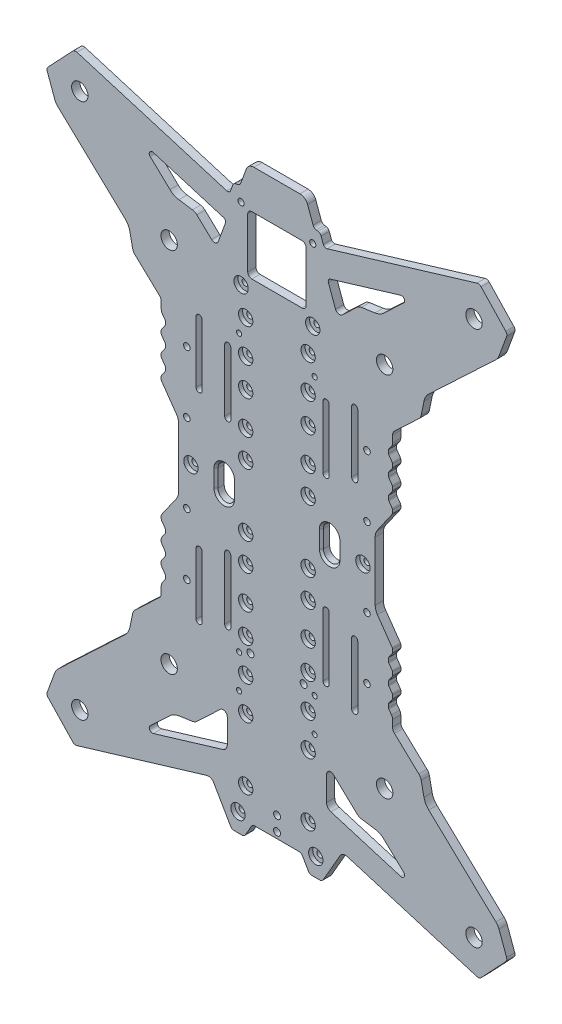
SolidWorks part; units mm, degrees
ref_plane "Front Plane" through (0, 0, 0) normal (0, 0, 1) x (1, 0, 0)
ref_plane "Top Plane" through (0, 0, 0) normal (0, 1, 0) x (1, 0, 0)
ref_plane "Right Plane" through (0, 0, 0) normal (1, 0, 0) x (0, 0, -1)
sketch "Model" plane through (0, 0, 0) normal (0, 0, 1) x (1, 0, 0)
  line L0 (183.8108, 197.417) -> (183.8108, 227.917)
  line L1 (186.8108, 227.917) -> (186.8108, 197.417)
  line L2 (138.8108, 139.917) -> (138.8108, 109.417)
  line L3 (135.8108, 109.417) -> (135.8108, 139.917)
  line L4 (186.8108, 139.917) -> (186.8108, 109.417)
  line L5 (183.8108, 109.417) -> (183.8108, 139.917)
  line L6 (135.8108, 197.417) -> (135.8108, 227.917)
  line L7 (138.8108, 227.917) -> (138.8108, 197.417)
  line L8 (147.0608, 264.0945) -> (147.0608, 288.5945)
  line L9 (173.5608, 262.0945) -> (149.0608, 262.0945)
  line L10 (175.5608, 288.5945) -> (175.5608, 264.0945)
  line L11 (149.0608, 290.5945) -> (173.5608, 290.5945)
  line L12 (133.6884, 72.3677) -> (122.1935, 61.5247)
  line L13 (120.0282, 60.4766) -> (113.4215, 59.5095)
  line L14 (100.8847, 45.7661) -> (134.926, 56.02)
  line L15 (209.2, 59.5095) -> (202.5933, 60.4766)
  line L16 (200.428, 61.5247) -> (188.9331, 72.3677)
  line L17 (185.5608, 58.8925) -> (185.5608, 70.9128)
  line L18 (187.6955, 56.02) -> (221.7368, 45.7661)
  line L19 (223.1987, 48.2935) -> (213.5306, 57.4133)
  line L20 (113.4215, 277.8244) -> (120.0282, 276.8573)
  line L21 (122.1935, 275.8092) -> (129.4288, 268.9842)
  line L22 (135.174, 281.2392) -> (100.8847, 291.5678)
  line L23 (99.4228, 289.0404) -> (109.0909, 279.9206)
  line L24 (261.0344, 314.783) -> (273.0616, 302.0327)
  line L25 (273.4849, 299.9728) -> (269.7846, 289.8648)
  line L26 (268.2674, 287.5628) -> (235.4884, 256.6428)
  line L27 (233.1432, 252.4417) -> (231.7925, 245.9027)
  line L28 (230.6199, 243.8022) -> (218.7522, 232.6075)
  line L29 (217.8108, 230.4252) -> (217.8108, 227.2161)
  line L30 (217.2682, 225.4954) -> (215.9916, 223.6722)
  line L31 (215.8108, 223.0986) -> (215.8108, 221.7292)
  line L32 (215.9916, 221.1557) -> (217.6299, 218.8159)
  line L33 (217.8108, 218.2423) -> (217.8108, 216.8729)
  line L34 (217.6299, 216.2994) -> (215.9916, 213.9596)
  line L35 (215.8108, 213.386) -> (215.8108, 212.0166)
  line L36 (215.9916, 211.4431) -> (217.6299, 209.1033)
  line L37 (217.8108, 208.5298) -> (217.8108, 207.1603)
  line L38 (217.6299, 206.5868) -> (215.9916, 204.247)
  line L39 (215.8108, 203.6735) -> (215.8108, 202.304)
  line L40 (215.9916, 201.7305) -> (217.6299, 199.3907)
  line L41 (217.8108, 198.8172) -> (217.8108, 197.4478)
  line L42 (217.6299, 196.8742) -> (210.3959, 186.5429)
  line L43 (209.3108, 183.1014) -> (209.3108, 154.2325)
  line L44 (210.3959, 150.791) -> (217.6299, 140.4597)
  line L45 (217.8108, 139.8861) -> (217.8108, 138.5167)
  line L46 (217.6299, 137.9432) -> (215.9916, 135.6034)
  line L47 (215.8108, 135.0299) -> (215.8108, 133.6605)
  line L48 (215.9916, 133.0869) -> (217.6299, 130.7471)
  line L49 (217.8108, 130.1736) -> (217.8108, 128.8042)
  line L50 (217.6299, 128.2306) -> (215.9916, 125.8908)
  line L51 (215.8108, 125.3173) -> (215.8108, 123.9479)
  line L52 (215.9916, 123.3743) -> (217.6299, 121.0345)
  line L53 (217.8108, 120.461) -> (217.8108, 119.0916)
  line L54 (217.6299, 118.518) -> (215.9916, 116.1782)
  line L55 (215.8108, 115.6047) -> (215.8108, 114.2353)
  line L56 (215.9916, 113.6617) -> (217.2682, 111.8385)
  line L57 (217.8108, 110.1178) -> (217.8108, 106.9087)
  line L58 (218.7522, 104.7264) -> (230.6199, 93.5317)
  line L59 (231.7925, 91.4312) -> (233.1432, 84.8922)
  line L60 (235.4884, 80.6911) -> (268.2674, 49.7711)
  line L61 (269.7846, 47.4691) -> (273.4849, 37.3611)
  line L62 (273.0616, 35.3012) -> (261.0344, 22.5509)
  line L63 (259.0027, 22.0083) -> (195.64, 41.0944)
  line L64 (192.1766, 39.7219) -> (183.942, 25.4591)
  line L65 (182.2099, 24.4591) -> (178.4116, 24.4591)
  line L66 (176.6796, 25.4591) -> (173.7928, 30.4591)
  line L67 (172.0608, 31.4591) -> (150.5608, 31.4591)
  line L68 (148.8287, 30.4591) -> (145.942, 25.4591)
  line L69 (144.2099, 24.4591) -> (140.4116, 24.4591)
  line L70 (138.6796, 25.4591) -> (130.4449, 39.7219)
  line L71 (126.9816, 41.0944) -> (63.6188, 22.0083)
  line L72 (61.5871, 22.5509) -> (49.5599, 35.3012)
  line L73 (49.1366, 37.3611) -> (52.8369, 47.4691)
  line L74 (54.3542, 49.7711) -> (87.1331, 80.6911)
  line L75 (89.4783, 84.8922) -> (90.8291, 91.4312)
  line L76 (92.0016, 93.5317) -> (103.8693, 104.7264)
  line L77 (104.8108, 106.9087) -> (104.8108, 110.1178)
  line L78 (105.3533, 111.8385) -> (106.6299, 113.6617)
  line L79 (106.8108, 114.2353) -> (106.8108, 115.6047)
  line L80 (106.6299, 116.1782) -> (104.9916, 118.518)
  line L81 (104.8108, 119.0916) -> (104.8108, 120.461)
  line L82 (104.9916, 121.0345) -> (106.6299, 123.3743)
  line L83 (106.6299, 125.8908) -> (104.9916, 128.2306)
  line L84 (104.8108, 128.8042) -> (104.8108, 130.1736)
  line L85 (104.9916, 130.7471) -> (106.6299, 133.0869)
  line L86 (106.8108, 133.6605) -> (106.8108, 135.0299)
  line L87 (106.6299, 135.6034) -> (104.9916, 137.9432)
  line L88 (104.8108, 138.5167) -> (104.8108, 139.8861)
  line L89 (104.9916, 140.4597) -> (112.2257, 150.791)
  line L90 (113.3108, 154.2325) -> (113.3108, 183.1014)
  line L91 (112.2257, 186.5429) -> (104.9916, 196.8742)
  line L92 (104.8108, 197.4478) -> (104.8108, 198.8172)
  line L93 (104.9916, 199.3907) -> (106.6299, 201.7305)
  line L94 (106.8108, 202.304) -> (106.8108, 203.6735)
  line L95 (106.6299, 204.247) -> (104.9916, 206.5868)
  line L96 (104.8108, 207.1603) -> (104.8108, 208.5298)
  line L97 (104.9916, 209.1033) -> (106.6299, 211.4431)
  line L98 (106.8108, 212.0166) -> (106.8108, 213.386)
  line L99 (106.6299, 213.9596) -> (104.9916, 216.2994)
  line L100 (104.8108, 216.8729) -> (104.8108, 218.2423)
  line L101 (104.9916, 218.8159) -> (106.6299, 221.1557)
  line L102 (106.8108, 221.7292) -> (106.8108, 223.0986)
  line L103 (106.6299, 223.6722) -> (105.3533, 225.4954)
  line L104 (104.8108, 227.2161) -> (104.8108, 230.4252)
  line L105 (103.8693, 232.6075) -> (92.0016, 243.8022)
  line L106 (90.8291, 245.9027) -> (89.4783, 252.4417)
  line L107 (87.1331, 256.6428) -> (54.3542, 287.5628)
  line L108 (52.8369, 289.8648) -> (49.1366, 299.9728)
  line L109 (49.5599, 302.0327) -> (61.5871, 314.783)
  line L110 (63.6188, 315.3256) -> (136.8099, 293.279)
  line L111 (138.6521, 294.2022) -> (139.728, 297.1583)
  line L112 (141.2601, 298.4439) -> (142.113, 298.5943)
  line L113 (143.6451, 299.8798) -> (146.325, 307.2429)
  line L114 (150.0838, 309.8748) -> (172.5378, 309.8748)
  line L115 (176.2965, 307.2429) -> (178.9765, 299.8798)
  line L116 (180.5086, 298.5943) -> (181.3614, 298.4439)
  line L117 (185.8116, 293.279) -> (259.0027, 315.3256)
  line L118 (193.1927, 268.9842) -> (200.428, 275.8092)
  line L119 (202.5933, 276.8573) -> (209.2, 277.8244)
  line L120 (221.7368, 291.5678) -> (187.4475, 281.2392)
  line L121 (186.4706, 279.2899) -> (189.941, 269.7551)
  line L122 (106.8108, 123.9479) -> (106.8108, 125.3173)
  line L123 (137.0608, 70.9128) -> (137.0608, 58.8925)
  line L124 (109.0909, 57.4133) -> (99.4228, 48.2935)
  line L125 (132.6805, 269.7551) -> (136.1509, 279.2899)
  line L126 (182.8935, 297.1583) -> (183.9694, 294.2022)
  line L127 (213.5306, 279.9206) -> (223.1987, 289.0404)
  circle A0 centre (178.8108, 292.022) radius 1.5
  arc A1 (183.8108, 197.417) -> (186.8108, 197.417) centre (185.3108, 197.417) ccw
  arc A2 (186.8108, 227.917) -> (183.8108, 227.917) centre (185.3108, 227.917) ccw
  arc A3 (138.8108, 139.917) -> (135.8108, 139.917) centre (137.3108, 139.917) ccw
  arc A4 (135.8108, 109.417) -> (138.8108, 109.417) centre (137.3108, 109.417) ccw
  circle A5 centre (213.9455, 258.3167) radius 4
  circle A6 centre (257.5914, 299.4875) radius 4
  circle A7 centre (65.0301, 299.4875) radius 4
  circle A8 centre (108.6761, 258.3167) radius 4
  circle A9 centre (108.6761, 79.0172) radius 4
  circle A10 centre (65.0301, 37.8464) radius 4
  circle A11 centre (257.5914, 37.8464) radius 4
  circle A12 centre (213.9455, 79.0172) radius 4
  arc A13 (186.8108, 139.917) -> (183.8108, 139.917) centre (185.3108, 139.917) ccw
  arc A14 (183.8108, 109.417) -> (186.8108, 109.417) centre (185.3108, 109.417) ccw
  arc A15 (135.8108, 197.417) -> (138.8108, 197.417) centre (137.3108, 197.417) ccw
  arc A16 (138.8108, 227.917) -> (135.8108, 227.917) centre (137.3108, 227.917) ccw
  circle A17 centre (143.8108, 292.022) radius 1.5
  arc A18 (147.0608, 264.0945) -> (149.0608, 262.0945) centre (149.0608, 264.0945) ccw
  arc A19 (173.5608, 262.0945) -> (175.5608, 264.0945) centre (173.5608, 264.0945) ccw
  arc A20 (175.5608, 288.5945) -> (173.5608, 290.5945) centre (173.5608, 288.5945) ccw
  arc A21 (149.0608, 290.5945) -> (147.0608, 288.5945) centre (149.0608, 288.5945) ccw
  circle A22 centre (146.0608, 227.917) radius 3.5 construction
  circle A23 centre (176.5608, 227.917) radius 3.5 construction
  circle A24 centre (176.5608, 197.417) radius 3.5 construction
  circle A25 centre (146.0608, 197.417) radius 3.5 construction
  circle A26 centre (119.3108, 168.667) radius 3.5 construction
  circle A27 centre (203.3108, 168.667) radius 3.5 construction
  circle A28 centre (146.0608, 183.917) radius 3.5 construction
  circle A29 centre (176.5608, 183.917) radius 3.5 construction
  circle A30 centre (146.0608, 153.417) radius 3.5 construction
  circle A31 centre (176.5608, 153.417) radius 3.5 construction
  circle A32 centre (146.0608, 139.917) radius 3.5 construction
  circle A33 centre (176.5608, 139.917) radius 3.5 construction
  circle A34 centre (146.0608, 109.417) radius 3.5 construction
  circle A35 centre (176.5608, 109.417) radius 3.5 construction
  circle A36 centre (146.0608, 76.667) radius 3.5 construction
  circle A37 centre (176.5608, 76.667) radius 3.5 construction
  circle A38 centre (146.0608, 46.167) radius 3.5 construction
  circle A39 centre (176.5608, 46.167) radius 3.5 construction
  circle A40 centre (142.3108, 33.4591) radius 3.5 construction
  circle A41 centre (180.3108, 33.4591) radius 3.5 construction
  circle A42 centre (176.5608, 93.042) radius 3.5 construction
  circle A43 centre (146.0608, 93.042) radius 3.5 construction
  circle A44 centre (176.5608, 123.542) radius 3.5 construction
  circle A45 centre (146.0608, 123.542) radius 3.5 construction
  circle A46 centre (176.5608, 213.792) radius 3.5 construction
  circle A47 centre (146.0608, 213.792) radius 3.5 construction
  circle A48 centre (176.5608, 244.292) radius 3.5 construction
  circle A49 centre (146.0608, 244.292) radius 3.5 construction
  circle A50 centre (178.8108, 257.022) radius 3.5 construction
  circle A51 centre (143.8108, 257.022) radius 3.5 construction
  arc A52 (137.0608, 70.9128) -> (133.6884, 72.3677) centre (135.0608, 70.9128) ccw
  arc A53 (120.0282, 60.4766) -> (122.1935, 61.5247) centre (119.4488, 64.4344) ccw
  arc A54 (113.4215, 59.5095) -> (109.0909, 57.4133) centre (114.5803, 51.5938) ccw
  arc A55 (99.4228, 48.2935) -> (100.8847, 45.7661) centre (100.4521, 47.2023) ccw
  arc A56 (134.926, 56.02) -> (137.0608, 58.8925) centre (134.0608, 58.8925) ccw
  arc A57 (200.428, 61.5247) -> (202.5933, 60.4766) centre (203.1727, 64.4344) ccw
  arc A58 (188.9331, 72.3677) -> (185.5608, 70.9128) centre (187.5608, 70.9128) ccw
  arc A59 (185.5608, 58.8925) -> (187.6955, 56.02) centre (188.5608, 58.8925) ccw
  arc A60 (221.7368, 45.7661) -> (223.1987, 48.2935) centre (222.1695, 47.2023) ccw
  arc A61 (213.5306, 57.4133) -> (209.2, 59.5095) centre (208.0412, 51.5938) ccw
  arc A62 (122.1935, 275.8092) -> (120.0282, 276.8573) centre (119.4488, 272.8995) ccw
  arc A63 (129.4288, 268.9842) -> (132.6805, 269.7551) centre (130.8012, 270.4391) ccw
  arc A64 (136.1509, 279.2899) -> (135.174, 281.2392) centre (134.7414, 279.8029) ccw
  arc A65 (100.8847, 291.5678) -> (99.4228, 289.0404) centre (100.4521, 290.1316) ccw
  arc A66 (109.0909, 279.9206) -> (113.4215, 277.8244) centre (114.5803, 285.7401) ccw
  arc A67 (261.0344, 314.783) -> (259.0027, 315.3256) centre (259.5795, 313.4106) ccw
  arc A68 (273.4849, 299.9728) -> (273.0616, 302.0327) centre (271.6068, 300.6603) ccw
  arc A69 (268.2674, 287.5628) -> (269.7846, 289.8648) centre (264.1503, 291.9274) ccw
  arc A70 (235.4884, 256.6428) -> (233.1432, 252.4417) centre (240.9778, 250.8233) ccw
  arc A71 (230.6199, 243.8022) -> (231.7925, 245.9027) centre (227.8752, 246.7119) ccw
  arc A72 (218.7522, 232.6075) -> (217.8108, 230.4252) centre (220.8108, 230.4252) ccw
  arc A73 (217.2682, 225.4954) -> (217.8108, 227.2161) centre (214.8108, 227.2161) ccw
  arc A74 (215.9916, 223.6722) -> (215.8108, 223.0986) centre (216.8108, 223.0986) ccw
  arc A75 (215.8108, 221.7292) -> (215.9916, 221.1557) centre (216.8108, 221.7292) ccw
  arc A76 (217.8108, 218.2423) -> (217.6299, 218.8159) centre (216.8108, 218.2423) ccw
  arc A77 (217.6299, 216.2994) -> (217.8108, 216.8729) centre (216.8108, 216.8729) ccw
  arc A78 (215.9916, 213.9596) -> (215.8108, 213.386) centre (216.8108, 213.386) ccw
  arc A79 (215.8108, 212.0166) -> (215.9916, 211.4431) centre (216.8108, 212.0166) ccw
  arc A80 (217.8108, 208.5298) -> (217.6299, 209.1033) centre (216.8108, 208.5298) ccw
  arc A81 (217.6299, 206.5868) -> (217.8108, 207.1603) centre (216.8108, 207.1603) ccw
  arc A82 (215.9916, 204.247) -> (215.8108, 203.6735) centre (216.8108, 203.6735) ccw
  arc A83 (215.8108, 202.304) -> (215.9916, 201.7305) centre (216.8108, 202.3041) ccw
  arc A84 (217.8108, 198.8172) -> (217.6299, 199.3907) centre (216.8108, 198.8172) ccw
  arc A85 (217.6299, 196.8742) -> (217.8108, 197.4478) centre (216.8108, 197.4478) ccw
  arc A86 (210.3959, 186.5429) -> (209.3108, 183.1014) centre (215.3108, 183.1014) ccw
  arc A87 (209.3108, 154.2325) -> (210.3959, 150.791) centre (215.3108, 154.2325) ccw
  arc A88 (217.8108, 139.8861) -> (217.6299, 140.4597) centre (216.8108, 139.8861) ccw
  arc A89 (217.6299, 137.9432) -> (217.8108, 138.5167) centre (216.8108, 138.5167) ccw
  arc A90 (215.9916, 135.6034) -> (215.8108, 135.0299) centre (216.8108, 135.0299) ccw
  arc A91 (215.8108, 133.6605) -> (215.9916, 133.0869) centre (216.8108, 133.6604) ccw
  arc A92 (217.8108, 130.1736) -> (217.6299, 130.7471) centre (216.8108, 130.1736) ccw
  arc A93 (217.6299, 128.2306) -> (217.8108, 128.8042) centre (216.8108, 128.8042) ccw
  arc A94 (215.9916, 125.8908) -> (215.8108, 125.3173) centre (216.8108, 125.3173) ccw
  arc A95 (215.8108, 123.9479) -> (215.9916, 123.3743) centre (216.8108, 123.9479) ccw
  arc A96 (217.8108, 120.461) -> (217.6299, 121.0345) centre (216.8108, 120.461) ccw
  arc A97 (217.6299, 118.518) -> (217.8108, 119.0916) centre (216.8108, 119.0916) ccw
  arc A98 (215.9916, 116.1782) -> (215.8108, 115.6047) centre (216.8108, 115.6047) ccw
  arc A99 (215.8108, 114.2353) -> (215.9916, 113.6617) centre (216.8108, 114.2353) ccw
  arc A100 (217.8108, 110.1178) -> (217.2682, 111.8385) centre (214.8108, 110.1178) ccw
  arc A101 (217.8108, 106.9087) -> (218.7522, 104.7264) centre (220.8108, 106.9087) ccw
  arc A102 (231.7925, 91.4312) -> (230.6199, 93.5317) centre (227.8752, 90.622) ccw
  arc A103 (233.1432, 84.8922) -> (235.4884, 80.6911) centre (240.9778, 86.5106) ccw
  arc A104 (269.7846, 47.4691) -> (268.2674, 49.7711) centre (264.1503, 45.4065) ccw
  arc A105 (273.0616, 35.3012) -> (273.4849, 37.3611) centre (271.6068, 36.6736) ccw
  arc A106 (259.0027, 22.0083) -> (261.0344, 22.5509) centre (259.5795, 23.9233) ccw
  arc A107 (195.64, 41.0944) -> (192.1766, 39.7219) centre (194.7747, 38.2219) ccw
  arc A108 (182.2099, 24.4591) -> (183.942, 25.4591) centre (182.2099, 26.4591) ccw
  arc A109 (176.6796, 25.4591) -> (178.4116, 24.4591) centre (178.4116, 26.4591) ccw
  arc A110 (173.7928, 30.4591) -> (172.0608, 31.4591) centre (172.0608, 29.4591) ccw
  arc A111 (150.5608, 31.4591) -> (148.8287, 30.4591) centre (150.5608, 29.4591) ccw
  arc A112 (144.2099, 24.4591) -> (145.942, 25.4591) centre (144.2099, 26.4591) ccw
  arc A113 (138.6796, 25.4591) -> (140.4116, 24.4591) centre (140.4116, 26.4591) ccw
  arc A114 (130.4449, 39.7219) -> (126.9816, 41.0944) centre (127.8468, 38.2219) ccw
  arc A115 (61.5871, 22.5509) -> (63.6188, 22.0083) centre (63.042, 23.9233) ccw
  arc A116 (49.1366, 37.3611) -> (49.5599, 35.3012) centre (51.0147, 36.6736) ccw
  arc A117 (54.3542, 49.7711) -> (52.8369, 47.4691) centre (58.4712, 45.4065) ccw
  arc A118 (87.1331, 80.6911) -> (89.4783, 84.8922) centre (81.6437, 86.5106) ccw
  arc A119 (92.0016, 93.5317) -> (90.8291, 91.4312) centre (94.7464, 90.622) ccw
  arc A120 (103.8693, 104.7264) -> (104.8108, 106.9087) centre (101.8108, 106.9087) ccw
  arc A121 (105.3533, 111.8385) -> (104.8108, 110.1178) centre (107.8108, 110.1178) ccw
  arc A122 (106.6299, 113.6617) -> (106.8108, 114.2353) centre (105.8108, 114.2353) ccw
  arc A123 (106.8108, 115.6047) -> (106.6299, 116.1782) centre (105.8108, 115.6047) ccw
  arc A124 (104.8108, 119.0916) -> (104.9916, 118.518) centre (105.8108, 119.0916) ccw
  arc A125 (104.9916, 121.0345) -> (104.8108, 120.461) centre (105.8108, 120.461) ccw
  arc A126 (106.6299, 123.3743) -> (106.8108, 123.9479) centre (105.8108, 123.9479) ccw
  arc A127 (106.8108, 125.3173) -> (106.6299, 125.8908) centre (105.8108, 125.3173) ccw
  arc A128 (104.8108, 128.8042) -> (104.9916, 128.2306) centre (105.8108, 128.8042) ccw
  arc A129 (104.9916, 130.7471) -> (104.8108, 130.1736) centre (105.8108, 130.1736) ccw
  arc A130 (106.6299, 133.0869) -> (106.8108, 133.6605) centre (105.8108, 133.6604) ccw
  arc A131 (106.8108, 135.0299) -> (106.6299, 135.6034) centre (105.8108, 135.0299) ccw
  arc A132 (104.8108, 138.5167) -> (104.9916, 137.9432) centre (105.8108, 138.5167) ccw
  arc A133 (104.9916, 140.4597) -> (104.8108, 139.8861) centre (105.8108, 139.8861) ccw
  arc A134 (112.2257, 150.791) -> (113.3108, 154.2325) centre (107.3108, 154.2325) ccw
  arc A135 (113.3108, 183.1014) -> (112.2257, 186.5429) centre (107.3108, 183.1014) ccw
  arc A136 (104.8108, 197.4478) -> (104.9916, 196.8742) centre (105.8108, 197.4478) ccw
  arc A137 (104.9916, 199.3907) -> (104.8108, 198.8172) centre (105.8108, 198.8172) ccw
  arc A138 (106.6299, 201.7305) -> (106.8108, 202.304) centre (105.8108, 202.3041) ccw
  arc A139 (106.8108, 203.6735) -> (106.6299, 204.247) centre (105.8108, 203.6735) ccw
  arc A140 (104.8108, 207.1603) -> (104.9916, 206.5868) centre (105.8108, 207.1603) ccw
  arc A141 (104.9916, 209.1033) -> (104.8108, 208.5298) centre (105.8108, 208.5298) ccw
  arc A142 (106.6299, 211.4431) -> (106.8108, 212.0166) centre (105.8108, 212.0166) ccw
  arc A143 (106.8108, 213.386) -> (106.6299, 213.9596) centre (105.8108, 213.386) ccw
  arc A144 (104.8108, 216.8729) -> (104.9916, 216.2994) centre (105.8108, 216.8729) ccw
  arc A145 (104.9916, 218.8159) -> (104.8108, 218.2423) centre (105.8108, 218.2423) ccw
  arc A146 (106.6299, 221.1557) -> (106.8108, 221.7292) centre (105.8108, 221.7292) ccw
  arc A147 (106.8108, 223.0986) -> (106.6299, 223.6722) centre (105.8108, 223.0986) ccw
  arc A148 (104.8108, 227.2161) -> (105.3533, 225.4954) centre (107.8108, 227.2161) ccw
  arc A149 (104.8108, 230.4252) -> (103.8693, 232.6075) centre (101.8108, 230.4252) ccw
  arc A150 (90.8291, 245.9027) -> (92.0016, 243.8022) centre (94.7464, 246.7119) ccw
  arc A151 (89.4783, 252.4417) -> (87.1331, 256.6428) centre (81.6437, 250.8233) ccw
  arc A152 (52.8369, 289.8648) -> (54.3542, 287.5628) centre (58.4712, 291.9274) ccw
  arc A153 (49.5599, 302.0327) -> (49.1366, 299.9728) centre (51.0147, 300.6603) ccw
  arc A154 (63.6188, 315.3256) -> (61.5871, 314.783) centre (63.042, 313.4106) ccw
  arc A155 (136.8099, 293.279) -> (138.6521, 294.2022) centre (137.2425, 294.7152) ccw
  arc A156 (141.2601, 298.4439) -> (139.728, 297.1583) centre (141.6074, 296.4743) ccw
  arc A157 (142.113, 298.5943) -> (143.6451, 299.8798) centre (141.7657, 300.5639) ccw
  arc A158 (150.0838, 309.8748) -> (146.325, 307.2429) centre (150.0838, 305.8748) ccw
  arc A159 (176.2965, 307.2429) -> (172.5378, 309.8748) centre (172.5378, 305.8748) ccw
  arc A160 (178.9765, 299.8798) -> (180.5086, 298.5943) centre (180.8559, 300.5639) ccw
  arc A161 (182.8935, 297.1583) -> (181.3614, 298.4439) centre (181.0141, 296.4743) ccw
  arc A162 (183.9694, 294.2022) -> (185.8116, 293.279) centre (185.379, 294.7152) ccw
  arc A163 (202.5933, 276.8573) -> (200.428, 275.8092) centre (203.1727, 272.8995) ccw
  arc A164 (209.2, 277.8244) -> (213.5306, 279.9206) centre (208.0412, 285.7401) ccw
  arc A165 (223.1987, 289.0404) -> (221.7368, 291.5678) centre (222.1695, 290.1316) ccw
  arc A166 (187.4475, 281.2392) -> (186.4706, 279.2899) centre (187.8801, 279.8029) ccw
  arc A167 (189.941, 269.7551) -> (193.1927, 268.9842) centre (191.8204, 270.4391) ccw
  circle A168 centre (176.5608, 227.917) radius 1.5
  circle A169 centre (146.0608, 227.917) radius 1.5
  circle A170 centre (146.0608, 123.542) radius 1.5
  circle A171 centre (176.5608, 123.542) radius 1.5
  circle A172 centre (146.0608, 93.042) radius 1.5
  circle A173 centre (176.5608, 93.042) radius 1.5
  circle A174 centre (180.3108, 33.4591) radius 1.5
  circle A175 centre (142.3108, 33.4591) radius 1.5
  circle A176 centre (176.5608, 76.667) radius 1.5
  circle A177 centre (146.0608, 76.667) radius 1.5
  circle A178 centre (146.0608, 109.417) radius 1.5
  circle A179 centre (119.3108, 168.667) radius 1.5
  circle A180 centre (176.5608, 139.917) radius 1.5
  circle A181 centre (146.0608, 139.917) radius 1.5
  circle A182 centre (146.0608, 213.792) radius 1.5
  circle A183 centre (176.5608, 213.792) radius 1.5
  circle A184 centre (176.5608, 109.417) radius 1.5
  circle A185 centre (176.5608, 197.417) radius 1.5
  circle A186 centre (176.5608, 244.292) radius 1.5
  circle A187 centre (203.3108, 168.667) radius 1.5
  circle A188 centre (143.8108, 257.022) radius 1.5
  circle A189 centre (178.8108, 257.022) radius 1.5
  circle A190 centre (146.0608, 244.292) radius 1.5
  circle A191 centre (146.0608, 46.167) radius 1.5
  circle A192 centre (146.0608, 197.417) radius 1.5
  circle A193 centre (176.5608, 46.167) radius 1.5
  circle A194 centre (146.0608, 183.917) radius 1.5
  circle A195 centre (146.0608, 153.417) radius 1.5
  circle A196 centre (176.5608, 153.417) radius 1.5
  circle A197 centre (176.5608, 183.917) radius 1.5
extrude "Main Body" add sketch "Model" along normal blind 4
sketch "Sketch2" plane through (0, 0, 4) normal (0, 0, 1) x (1, 0, 0)
  circle A0 centre (176.5608, 46.167) radius 3.5 construction
  circle A1 centre (180.3108, 33.4591) radius 3.5 construction
  circle A2 centre (142.3108, 33.4591) radius 3.5 construction
  circle A3 centre (146.0608, 46.167) radius 3.5 construction
  circle A4 centre (176.5608, 76.667) radius 3.5 construction
  circle A5 centre (146.0608, 76.667) radius 3.5 construction
  circle A6 centre (146.0608, 93.042) radius 3.5 construction
  circle A7 centre (176.5608, 93.042) radius 3.5 construction
  circle A8 centre (176.5608, 109.417) radius 3.5 construction
  circle A9 centre (146.0608, 109.417) radius 3.5 construction
  circle A10 centre (176.5608, 123.542) radius 3.5 construction
  circle A11 centre (146.0608, 123.542) radius 3.5 construction
  circle A12 centre (146.0608, 139.917) radius 3.5 construction
  circle A13 centre (176.5608, 139.917) radius 3.5 construction
  circle A14 centre (176.5608, 139.917) radius 1.5 construction
  circle A15 centre (203.3108, 168.667) radius 3.5 construction
  circle A16 centre (176.5608, 153.417) radius 3.5 construction
  circle A17 centre (146.0608, 153.417) radius 3.5 construction
  circle A18 centre (119.3108, 168.667) radius 3.5 construction
  circle A19 centre (146.0608, 183.917) radius 3.5 construction
  circle A20 centre (176.5608, 183.917) radius 3.5 construction
  circle A21 centre (176.5608, 197.417) radius 3.5 construction
  circle A22 centre (146.0608, 197.417) radius 3.5 construction
  circle A23 centre (176.5608, 213.792) radius 3.5 construction
  circle A24 centre (146.0608, 213.792) radius 3.5 construction
  circle A25 centre (146.0608, 227.917) radius 3.5 construction
  circle A26 centre (176.5608, 227.917) radius 3.5 construction
  circle A27 centre (176.5608, 244.292) radius 3.5 construction
  circle A28 centre (178.8108, 257.022) radius 3.5 construction
  circle A29 centre (146.0608, 244.292) radius 3.5 construction
  circle A30 centre (143.8108, 257.022) radius 3.5 construction
  circle A31 centre (176.5608, 46.167) radius 3.5
  circle A32 centre (180.3108, 33.4591) radius 3.5
  circle A33 centre (142.3108, 33.4591) radius 3.5
  circle A34 centre (146.0608, 46.167) radius 3.5
  circle A35 centre (176.5608, 76.667) radius 3.5
  circle A36 centre (146.0608, 76.667) radius 3.5
  circle A37 centre (146.0608, 93.042) radius 3.5
  circle A38 centre (176.5608, 93.042) radius 3.5
  circle A39 centre (176.5608, 109.417) radius 3.5
  circle A40 centre (146.0608, 109.417) radius 3.5
  circle A41 centre (176.5608, 123.542) radius 3.5
  circle A42 centre (146.0608, 123.542) radius 3.5
  circle A43 centre (146.0608, 139.917) radius 3.5
  circle A44 centre (176.5608, 139.917) radius 3.5
  circle A45 centre (176.5608, 139.917) radius 1.5
  circle A46 centre (203.3108, 168.667) radius 3.5
  circle A47 centre (176.5608, 153.417) radius 3.5
  circle A48 centre (146.0608, 153.417) radius 3.5
  circle A49 centre (119.3108, 168.667) radius 3.5
  circle A50 centre (146.0608, 183.917) radius 3.5
  circle A51 centre (176.5608, 183.917) radius 3.5
  circle A52 centre (176.5608, 197.417) radius 3.5
  circle A53 centre (146.0608, 197.417) radius 3.5
  circle A54 centre (176.5608, 213.792) radius 3.5
  circle A55 centre (146.0608, 213.792) radius 3.5
  circle A56 centre (146.0608, 227.917) radius 3.5
  circle A57 centre (176.5608, 227.917) radius 3.5
  circle A58 centre (176.5608, 244.292) radius 3.5
  circle A59 centre (178.8108, 257.022) radius 3.5
  circle A60 centre (146.0608, 244.292) radius 3.5
  circle A61 centre (143.8108, 257.022) radius 3.5
extrude "  Lower Fixture Point Countersink" cut sketch "Sketch2" against normal blind 2
sketch "Sketch3" plane through (0, 0, 0) normal (0, 0, -1) x (-1, 0, 0)
  line L0 (-124.8108, 134.6669) -> (-124.8108, 104.6669) construction
  line L1 (-121.8108, 104.6669) -> (-121.8108, 134.6669) construction
  line L2 (-124.8108, 232.667) -> (-124.8108, 202.667) construction
  line L3 (-121.8108, 202.667) -> (-121.8108, 232.667) construction
  line L4 (-200.8108, 232.667) -> (-200.8108, 202.667) construction
  line L5 (-197.8108, 202.667) -> (-197.8108, 232.667) construction
  line L6 (-197.8108, 104.6669) -> (-197.8108, 134.6669) construction
  line L7 (-200.8108, 134.6669) -> (-200.8108, 104.6669) construction
  line L8 (-124.8108, 134.6669) -> (-124.8108, 104.6669)
  line L9 (-121.8108, 104.6669) -> (-121.8108, 134.6669)
  line L10 (-124.8108, 232.667) -> (-124.8108, 202.667)
  line L11 (-121.8108, 202.667) -> (-121.8108, 232.667)
  line L12 (-200.8108, 232.667) -> (-200.8108, 202.667)
  line L13 (-197.8108, 202.667) -> (-197.8108, 232.667)
  line L14 (-197.8108, 104.6669) -> (-197.8108, 134.6669)
  line L15 (-200.8108, 134.6669) -> (-200.8108, 104.6669)
  arc A0 (-124.8108, 104.6669) -> (-121.8108, 104.6669) centre (-123.3108, 104.6669) ccw construction
  arc A1 (-121.8108, 134.6669) -> (-124.8108, 134.6669) centre (-123.3108, 134.6669) ccw construction
  arc A2 (-124.8108, 202.667) -> (-121.8108, 202.667) centre (-123.3108, 202.667) ccw construction
  arc A3 (-121.8108, 232.667) -> (-124.8108, 232.667) centre (-123.3108, 232.667) ccw construction
  arc A4 (-197.8108, 232.667) -> (-200.8108, 232.667) centre (-199.3108, 232.667) ccw construction
  arc A5 (-200.8108, 202.667) -> (-197.8108, 202.667) centre (-199.3108, 202.667) ccw construction
  arc A6 (-200.8108, 104.6669) -> (-197.8108, 104.6669) centre (-199.3108, 104.6669) ccw construction
  arc A7 (-197.8108, 134.6669) -> (-200.8108, 134.6669) centre (-199.3108, 134.6669) ccw construction
  arc A8 (-124.8108, 104.6669) -> (-121.8108, 104.6669) centre (-123.3108, 104.6669) ccw
  arc A9 (-121.8108, 134.6669) -> (-124.8108, 134.6669) centre (-123.3108, 134.6669) ccw
  arc A10 (-124.8108, 202.667) -> (-121.8108, 202.667) centre (-123.3108, 202.667) ccw
  arc A11 (-121.8108, 232.667) -> (-124.8108, 232.667) centre (-123.3108, 232.667) ccw
  arc A12 (-197.8108, 232.667) -> (-200.8108, 232.667) centre (-199.3108, 232.667) ccw
  arc A13 (-200.8108, 202.667) -> (-197.8108, 202.667) centre (-199.3108, 202.667) ccw
  arc A14 (-200.8108, 104.6669) -> (-197.8108, 104.6669) centre (-199.3108, 104.6669) ccw
  arc A15 (-197.8108, 134.6669) -> (-200.8108, 134.6669) centre (-199.3108, 134.6669) ccw
extrude "Extra Battery Strap Fixtures" cut sketch "Sketch3" against normal up to next
sketch "Sketch4" plane through (0, 0, 0) normal (0, 0, -1) x (-1, 0, 0)
  line L0 (-187.0608, 164.417) -> (-187.0608, 172.917) construction
  line L1 (-191.0608, 164.417) -> (-191.0608, 172.917)
  line L2 (-183.0608, 164.417) -> (-183.0608, 172.917)
  line L3 (-135.5608, 172.917) -> (-135.5608, 164.417) construction
  line L4 (-131.5608, 172.917) -> (-131.5608, 164.417)
  line L5 (-139.5608, 172.917) -> (-139.5608, 164.417)
  circle A0 centre (-187.0608, 172.917) radius 1.6 construction
  circle A1 centre (-187.0608, 164.417) radius 1.6 construction
  circle A2 centre (-135.5608, 172.917) radius 1.6 construction
  circle A3 centre (-135.5608, 164.417) radius 1.6 construction
  circle A4 centre (-187.0608, 172.917) radius 1.6 construction
  circle A5 centre (-187.0608, 164.417) radius 1.6 construction
  circle A6 centre (-135.5608, 172.917) radius 1.6 construction
  circle A7 centre (-135.5608, 164.417) radius 1.6 construction
  arc A8 (-191.0608, 164.417) -> (-183.0608, 164.417) centre (-187.0608, 164.417) ccw
  arc A9 (-183.0608, 172.917) -> (-191.0608, 172.917) centre (-187.0608, 172.917) ccw
  arc A10 (-131.5608, 172.917) -> (-139.5608, 172.917) centre (-135.5608, 172.917) ccw
  arc A11 (-139.5608, 164.417) -> (-131.5608, 164.417) centre (-135.5608, 164.417) ccw
  point P12 (-187.0608, 168.667)
  point P17 (-135.5608, 168.667)
  dimension "D1" = 8
extrude "Battery Cable Ingress" cut sketch "Sketch4" against normal up to next
chamfer "Battery Cable Ingress Chamfer" distance 1 angle 45 4 edges at (131.5608, 168.667, 4) (139.5608, 168.667, 4) (183.0608, 168.667, 4) (191.0608, 168.667, 4) tangent propagation no
sketch "Sketch5" plane through (0, 0, 0) normal (0, 0, -1) x (-1, 0, 0)
  line L0 (-161.3108, 262.0945) -> (-161.3108, 31.4591) construction
  line L1 (-149.0608, 262.0945) -> (-173.5608, 262.0945) construction
  line L2 (-150.5608, 31.4591) -> (-172.0608, 31.4591) construction
  line L3 (-146.0608, 109.417) -> (-146.0608, 93.042) construction
  line L4 (-146.0608, 93.042) -> (-146.0608, 76.667) construction
  line L5 (-179.7608, 101.2295) -> (-142.8608, 101.2295) construction
  line L6 (-179.7608, 84.8545) -> (-142.8608, 84.8545) construction
  line L7 (-179.7608, 236.1045) -> (-142.8608, 236.1045) construction
  line L8 (-146.0608, 244.292) -> (-146.0608, 227.917) construction
  circle A4 centre (-142.8608, 84.8545) radius 1.25
  circle A5 centre (-142.8608, 101.2295) radius 1.25
  circle A6 centre (-142.8608, 236.1045) radius 1.25
  circle A7 centre (-179.7608, 236.1045) radius 1.25
  circle A8 centre (-179.7608, 101.2295) radius 1.25
  circle A9 centre (-179.7608, 84.8545) radius 1.25
  point P24 (-146.0608, 84.8545)
  point P25 (-146.0608, 101.2295)
  point P30 (-146.0608, 236.1045)
  dimension "D1" = 2.5
  dimension "D2" = 36.9
  dimension "D3" = 36.9
  dimension "D4" = 36.9
extrude "Mauch PL200 Mounting Points" cut sketch "Sketch5" against normal up to next
sketch "Sketch6" plane through (0, 0, 0) normal (0, 0, -1) x (-1, 0, 0)
  circle A0 centre (-174.3688, 103.4113) radius 1.7 construction
  circle A1 centre (-148.3688, 103.4113) radius 1.7 construction
  circle A2 centre (-161.3688, 34.4113) radius 1.7 construction
  circle A3 centre (-161.3688, 41.4113) radius 2.25 construction
  circle A4 centre (-174.3688, 103.4113) radius 1.7
  circle A5 centre (-148.3688, 103.4113) radius 1.7
  circle A6 centre (-161.3688, 34.4113) radius 1.7
  circle A7 centre (-161.3688, 41.4113) radius 2.25 construction
  circle A8 centre (-161.3688, 41.4113) radius 1.7
  dimension "D1" = 3.4
extrude "RFD Carrier Mounting Points" cut sketch "Sketch6" against normal up to next
sketch "Sketch7" plane through (0, 0, 0) normal (0, 0, -1) x (-1, 0, 0)
  circle A0 centre (-205.3108, 217.6395) radius 1.6 construction
  circle A1 centre (-205.3108, 187.6395) radius 1.6 construction
  circle A2 centre (-205.3108, 149.1395) radius 1.6 construction
  circle A3 centre (-205.3108, 119.1395) radius 1.6 construction
  circle A4 centre (-117.3108, 119.1395) radius 1.6 construction
  circle A5 centre (-117.3108, 149.1395) radius 1.6 construction
  circle A6 centre (-117.3108, 187.6395) radius 1.6 construction
  circle A7 centre (-117.3108, 217.6395) radius 1.6 construction
  circle A8 centre (-205.3108, 217.6395) radius 1.6
  circle A9 centre (-205.3108, 187.6395) radius 1.6
  circle A10 centre (-205.3108, 149.1395) radius 1.6
  circle A11 centre (-205.3108, 119.1395) radius 1.6
  circle A12 centre (-117.3108, 119.1395) radius 1.6
  circle A13 centre (-117.3108, 149.1395) radius 1.6
  circle A14 centre (-117.3108, 187.6395) radius 1.6
  circle A15 centre (-117.3108, 217.6395) radius 1.6
extrude "ESC Carrier Fixtures Points" cut sketch "Sketch7" against normal up to next
